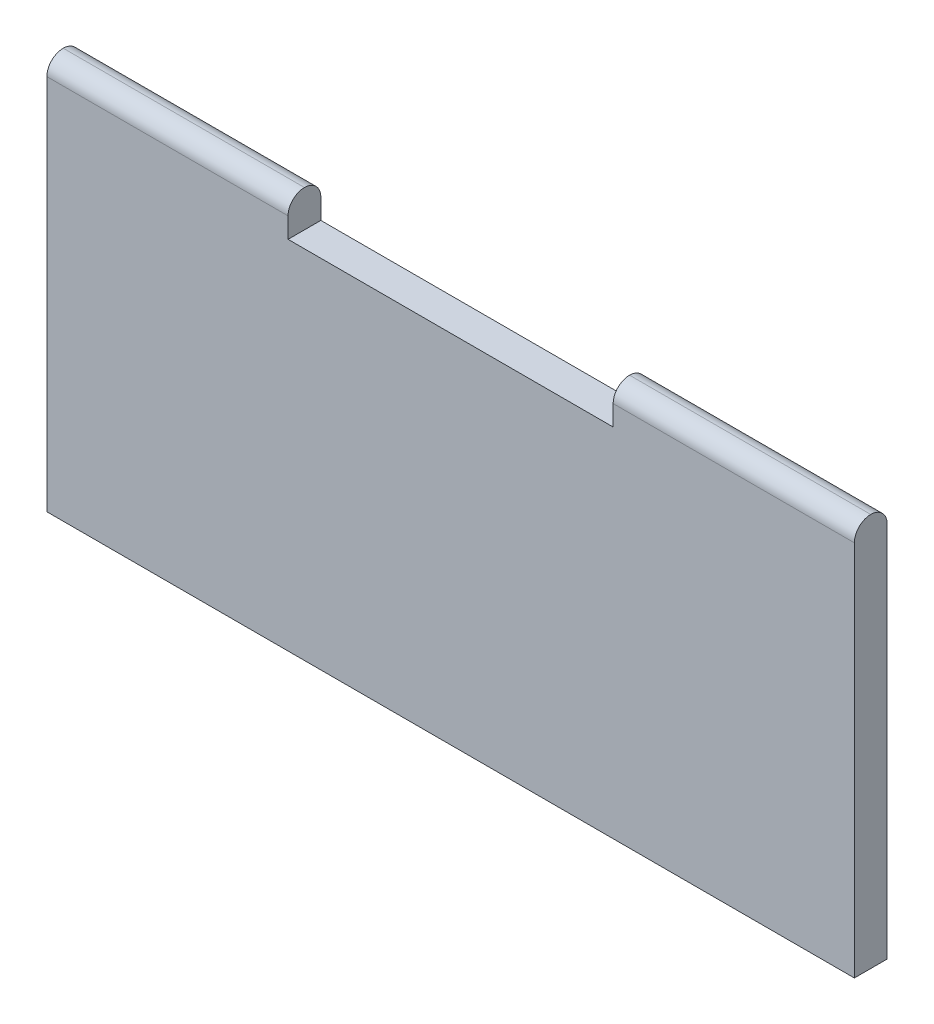
SolidWorks part; units mm, degrees
ref_plane "前视基准面" through (0, 0, 0) normal (0, 0, 1) x (1, 0, 0)
ref_plane "上视基准面" through (0, 0, 0) normal (0, 1, 0) x (1, 0, 0)
ref_plane "右视基准面" through (0, 0, 0) normal (1, 0, 0) x (0, 0, -1)
sketch "草图1" plane through (0, 0, 0) normal (0, 0, 1) x (1, 0, 0)
  line L1 (0, 0) -> (308, 0)
  line L2 (0, 0) -> (0, 150)
  line L3 (0, 150) -> (308, 150)
  line L4 (308, 0) -> (308, 150)
extrude "凸台-拉伸1" add sketch "草图1" along normal blind 12.5
fillet "圆角1" radius 6.25 1 edges at (154, 150, 12.5)
fillet "圆角2" radius 6.25 1 edges at (154, 150, 0)
sketch "草图2" plane through (0, 0, 0) normal (0, 0, -1) x (-1, 0, 0)
  line L2 (-154, 136) -> (-92, 136)
  line L3 (-154, 136) -> (-216, 136)
  line L4 (-216, 136) -> (-216, 165.9286)
  line L5 (-216, 165.9286) -> (-92, 165.9286)
  line L6 (-92, 165.9286) -> (-92, 136)
extrude "切除-拉伸1" cut sketch "草图2" against normal blind 44
